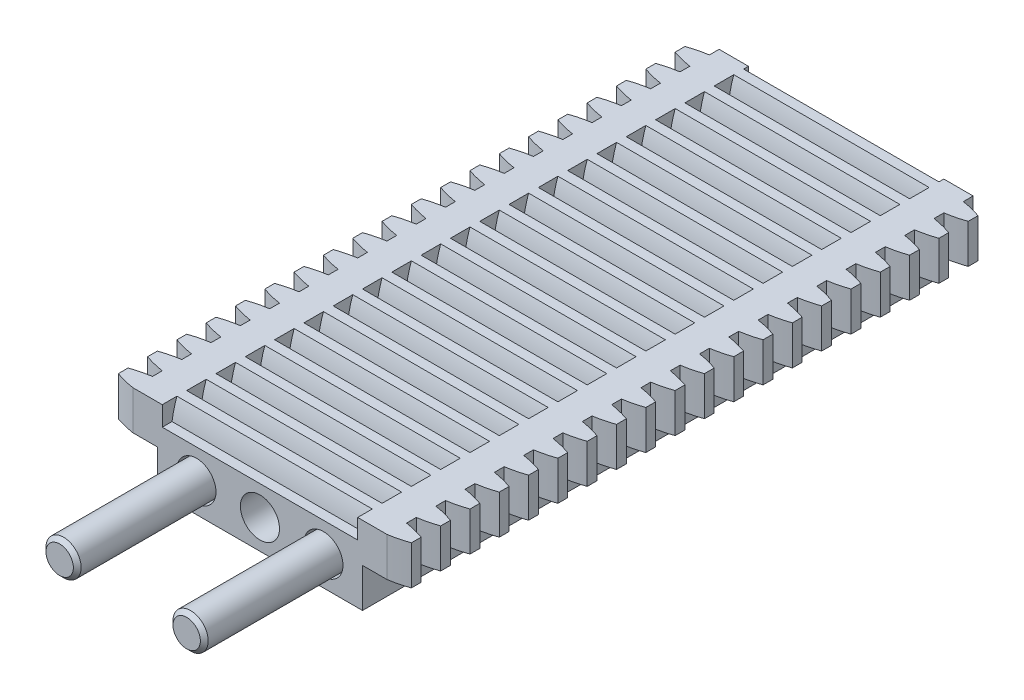
SolidWorks part; units mm, degrees
ref_plane "前视基准面" through (0, 0, 0) normal (0, 0, 1) x (1, 0, 0)
ref_plane "上视基准面" through (0, 0, 0) normal (0, 1, 0) x (1, 0, 0)
ref_plane "右视基准面" through (0, 0, 0) normal (1, 0, 0) x (0, 0, -1)
sketch "草图1" plane through (0, 0, 0) normal (0, 0, 1) x (1, 0, 0)
  line L0 (5.25, 2) -> (6.5, 2)
  line L1 (-5.25, 0) -> (5.25, 0)
  line L2 (-5.25, 0) -> (-5.25, 2)
  line L4 (5.25, 0) -> (5.25, 2)
  line L5 (-6.5, 2) -> (-5.25, 2)
  line L6 (-6.5, 2) -> (-6.5, 4)
  line L7 (-6.5, 4) -> (6.5, 4)
  line L8 (6.5, 2) -> (6.5, 4)
extrude "凸台-拉伸1" add sketch "草图1" against normal blind 60
sketch "草图2" plane through (0, 0, 0) normal (0, 0, 1) x (1, 0, 0)
  line L0 (-1.95, -2.5) -> (-1.1658, -2.5)
  line L1 (-1.95, -2.5) -> (-1.95, -1.5556)
  line L2 (-5.25, 0) -> (5.25, 0) construction
  line L3 (1.95, -2.5) -> (1.95, -1.5556)
  line L4 (0, 0) -> (-1.1658, -2.5)
  line L5 (-1.5, 0) -> (0, 0)
  line L6 (-1.5, 0) -> (-1.5, -0.6771)
  line L7 (0, 0) -> (1.1658, -2.5)
  line L8 (1.5, 0) -> (1.5, -0.6771)
  line L9 (1.1658, -2.5) -> (1.95, -2.5)
  line L10 (0, 0) -> (1.5, 0)
  arc A0 (-1.5, -0.6771) -> (-1.95, -1.5556) centre (0, -2) ccw
  arc A2 (1.95, -1.5556) -> (1.5, -0.6771) centre (0, -2) ccw
  line M2 (-5.25, 0) -> (5.25, 0)
extrude "凸台-拉伸2" add sketch "草图2" against normal blind 54 from offset 3 contours L6 A0 L1 L0 L4 M2 | L3 A2 L8 L7 L9 M2 region at (-1.1423, -1.1553, 0) region at (1.1423, -1.1553, 0) offset against normal yes
sketch "草图3" plane through (0, 0, 0) normal (0, 0, 1) x (1, 0, 0)
  circle A0 centre (-3.25, 1.5) radius 1
  circle A1 centre (0, 1.5) radius 1
  circle A2 centre (3.25, 1.5) radius 1
extrude "切除-拉伸1" cut sketch "草图3" against normal through all
sketch "草图4" plane through (0, 0, 0) normal (0, 0, 1) x (1, 0, 0)
  circle A0 centre (-3.25, 1.5) radius 0.9
  circle A1 centre (3.25, 1.5) radius 0.9
extrude "凸台-拉伸3" add sketch "草图4" along normal blind 7 and the other way blind 7 separate body
fillet "圆角1" radius 0.1 8 edges at (-1.1658, -2.5, -30) (-1.5579, -2.5, -57) (-1.95, -2.5, -30) (-1.5579, -2.5, -3) (1.95, -2.5, -30) (1.5579, -2.5, -57) (1.1658, -2.5, -30) (1.5579, -2.5, -3)
chamfer "倒角2" distance 0.2 angle 45 1 edges at (-2.35, 1.5, 7)
chamfer "倒角3" distance 0.2 angle 45 1 edges at (4.15, 1.5, 7)
sketch "草图6" plane through (0, 4, 0) normal (0, 1, 0) x (1, 0, 0)
  line L0 (-6.5, 59.5) -> (-6.5, 58.5)
  line L1 (-6.5, 60) -> (-6.5, 0) construction
  line L2 (-6.5, 58) -> (-6.5, 57)
  line L3 (-7.5, 59.25) -> (-7.5, 58.75)
  line L4 (-7.5, 57.75) -> (-7.5, 57.25)
  line L5 (-7.5, 56.25) -> (-7.5, 55.75)
  line L6 (-6.5, 56.5) -> (-6.5, 55.5)
  line L7 (-7.5, 54.75) -> (-7.5, 54.25)
  line L8 (-6.5, 55) -> (-6.5, 54)
  line L9 (-7.5, 53.25) -> (-7.5, 52.75)
  line L10 (-6.5, 53.5) -> (-6.5, 52.5)
  line L11 (-7.5, 51.75) -> (-7.5, 51.25)
  line L12 (-6.5, 52) -> (-6.5, 51)
  line L13 (-7.5, 50.25) -> (-7.5, 49.75)
  line L14 (-6.5, 50.5) -> (-6.5, 49.5)
  line L15 (-7.5, 48.75) -> (-7.5, 48.25)
  line L16 (-6.5, 49) -> (-6.5, 48)
  line L17 (-7.5, 47.25) -> (-7.5, 46.75)
  line L18 (-6.5, 47.5) -> (-6.5, 46.5)
  line L19 (-7.5, 45.75) -> (-7.5, 45.25)
  line L20 (-6.5, 46) -> (-6.5, 45)
  line L21 (-7.5, 44.25) -> (-7.5, 43.75)
  line L22 (-6.5, 44.5) -> (-6.5, 43.5)
  line L23 (-7.5, 42.75) -> (-7.5, 42.25)
  line L24 (-6.5, 43) -> (-6.5, 42)
  line L25 (-7.5, 41.25) -> (-7.5, 40.75)
  line L26 (-6.5, 41.5) -> (-6.5, 40.5)
  line L27 (-7.5, 39.75) -> (-7.5, 39.25)
  line L28 (-6.5, 40) -> (-6.5, 39)
  line L29 (-7.5, 38.25) -> (-7.5, 37.75)
  line L30 (-6.5, 38.5) -> (-6.5, 37.5)
  line L31 (-7.5, 36.75) -> (-7.5, 36.25)
  line L32 (-6.5, 37) -> (-6.5, 36)
  line L33 (-7.5, 35.25) -> (-7.5, 34.75)
  line L34 (-6.5, 35.5) -> (-6.5, 34.5)
  line L35 (-7.5, 33.75) -> (-7.5, 33.25)
  line L36 (-6.5, 34) -> (-6.5, 33)
  line L37 (-7.5, 32.25) -> (-7.5, 31.75)
  line L38 (-6.5, 32.5) -> (-6.5, 31.5)
  line L39 (-7.5, 30.75) -> (-7.5, 30.25)
  line L40 (-6.5, 31) -> (-6.5, 30)
  line L41 (-7.5, 29.25) -> (-7.5, 28.75)
  line L42 (-6.5, 29.5) -> (-6.5, 28.5)
  line L43 (-7.5, 27.75) -> (-7.5, 27.25)
  line L44 (-6.5, 28) -> (-6.5, 27)
  line L45 (-7.5, 26.25) -> (-7.5, 25.75)
  line L46 (-6.5, 26.5) -> (-6.5, 25.5)
  line L47 (-7.5, 24.75) -> (-7.5, 24.25)
  line L48 (-6.5, 25) -> (-6.5, 24)
  line L49 (-7.5, 23.25) -> (-7.5, 22.75)
  line L50 (-6.5, 23.5) -> (-6.5, 22.5)
  line L51 (-7.5, 21.75) -> (-7.5, 21.25)
  line L52 (-6.5, 22) -> (-6.5, 21)
  line L53 (-7.5, 20.25) -> (-7.5, 19.75)
  line L54 (-6.5, 20.5) -> (-6.5, 19.5)
  line L55 (-7.5, 18.75) -> (-7.5, 18.25)
  line L56 (-6.5, 19) -> (-6.5, 18)
  line L57 (-7.5, 17.25) -> (-7.5, 16.75)
  line L58 (-6.5, 17.5) -> (-6.5, 16.5)
  line L59 (-7.5, 15.75) -> (-7.5, 15.25)
  line L60 (-6.5, 16) -> (-6.5, 15)
  line L61 (-7.5, 14.25) -> (-7.5, 13.75)
  line L62 (-6.5, 14.5) -> (-6.5, 13.5)
  line L63 (-7.5, 12.75) -> (-7.5, 12.25)
  line L64 (-6.5, 13) -> (-6.5, 12)
  line L65 (-7.5, 11.25) -> (-7.5, 10.75)
  line L66 (-6.5, 11.5) -> (-6.5, 10.5)
  line L67 (-7.5, 9.75) -> (-7.5, 9.25)
  line L68 (-6.5, 10) -> (-6.5, 9)
  line L69 (-7.5, 8.25) -> (-7.5, 7.75)
  line L70 (-6.5, 8.5) -> (-6.5, 7.5)
  line L71 (-7.5, 6.75) -> (-7.5, 6.25)
  line L72 (-6.5, 7) -> (-6.5, 6)
  line L73 (-7.5, 5.25) -> (-7.5, 4.75)
  line L74 (-6.5, 5.5) -> (-6.5, 4.5)
  line L75 (-7.5, 3.75) -> (-7.5, 3.25)
  line L76 (-6.5, 4) -> (-6.5, 3)
  line L77 (-7.5, 2.25) -> (-7.5, 1.75)
  line L78 (-6.5, 2.5) -> (-6.5, 1.5)
  line L79 (-6.5, 1) -> (-6.5, 0)
  line L80 (-7.5, 0.75) -> (-7.5, 0.25)
  line L81 (0, 62.425) -> (0, -2.925) construction
  line L82 (7.5, 0.75) -> (7.5, 0.25)
  line L83 (6.5, 1) -> (6.5, 0)
  line L84 (6.5, 2.5) -> (6.5, 1.5)
  line L85 (7.5, 2.25) -> (7.5, 1.75)
  line L86 (6.5, 4) -> (6.5, 3)
  line L87 (7.5, 3.75) -> (7.5, 3.25)
  line L88 (6.5, 5.5) -> (6.5, 4.5)
  line L89 (7.5, 5.25) -> (7.5, 4.75)
  line L90 (6.5, 7) -> (6.5, 6)
  line L91 (7.5, 6.75) -> (7.5, 6.25)
  line L92 (6.5, 8.5) -> (6.5, 7.5)
  line L93 (7.5, 8.25) -> (7.5, 7.75)
  line L94 (6.5, 10) -> (6.5, 9)
  line L95 (7.5, 9.75) -> (7.5, 9.25)
  line L96 (6.5, 11.5) -> (6.5, 10.5)
  line L97 (7.5, 11.25) -> (7.5, 10.75)
  line L98 (6.5, 13) -> (6.5, 12)
  line L99 (7.5, 12.75) -> (7.5, 12.25)
  line L100 (6.5, 14.5) -> (6.5, 13.5)
  line L101 (7.5, 14.25) -> (7.5, 13.75)
  line L102 (6.5, 16) -> (6.5, 15)
  line L103 (7.5, 15.75) -> (7.5, 15.25)
  line L104 (6.5, 17.5) -> (6.5, 16.5)
  line L105 (7.5, 17.25) -> (7.5, 16.75)
  line L106 (6.5, 19) -> (6.5, 18)
  line L107 (7.5, 18.75) -> (7.5, 18.25)
  line L108 (6.5, 20.5) -> (6.5, 19.5)
  line L109 (7.5, 20.25) -> (7.5, 19.75)
  line L110 (6.5, 22) -> (6.5, 21)
  line L111 (7.5, 21.75) -> (7.5, 21.25)
  line L112 (6.5, 23.5) -> (6.5, 22.5)
  line L113 (7.5, 23.25) -> (7.5, 22.75)
  line L114 (6.5, 25) -> (6.5, 24)
  line L115 (7.5, 24.75) -> (7.5, 24.25)
  line L116 (6.5, 26.5) -> (6.5, 25.5)
  line L117 (7.5, 26.25) -> (7.5, 25.75)
  line L118 (6.5, 28) -> (6.5, 27)
  line L119 (7.5, 27.75) -> (7.5, 27.25)
  line L120 (6.5, 29.5) -> (6.5, 28.5)
  line L121 (7.5, 29.25) -> (7.5, 28.75)
  line L122 (6.5, 31) -> (6.5, 30)
  line L123 (7.5, 30.75) -> (7.5, 30.25)
  line L124 (6.5, 32.5) -> (6.5, 31.5)
  line L125 (7.5, 32.25) -> (7.5, 31.75)
  line L126 (6.5, 34) -> (6.5, 33)
  line L127 (7.5, 33.75) -> (7.5, 33.25)
  line L128 (6.5, 35.5) -> (6.5, 34.5)
  line L129 (7.5, 35.25) -> (7.5, 34.75)
  line L130 (6.5, 37) -> (6.5, 36)
  line L131 (7.5, 36.75) -> (7.5, 36.25)
  line L132 (6.5, 38.5) -> (6.5, 37.5)
  line L133 (7.5, 38.25) -> (7.5, 37.75)
  line L134 (6.5, 40) -> (6.5, 39)
  line L135 (7.5, 39.75) -> (7.5, 39.25)
  line L136 (6.5, 41.5) -> (6.5, 40.5)
  line L137 (7.5, 41.25) -> (7.5, 40.75)
  line L138 (6.5, 43) -> (6.5, 42)
  line L139 (7.5, 42.75) -> (7.5, 42.25)
  line L140 (6.5, 44.5) -> (6.5, 43.5)
  line L141 (7.5, 44.25) -> (7.5, 43.75)
  line L142 (6.5, 46) -> (6.5, 45)
  line L143 (7.5, 45.75) -> (7.5, 45.25)
  line L144 (6.5, 47.5) -> (6.5, 46.5)
  line L145 (7.5, 47.25) -> (7.5, 46.75)
  line L146 (6.5, 49) -> (6.5, 48)
  line L147 (7.5, 48.75) -> (7.5, 48.25)
  line L148 (6.5, 50.5) -> (6.5, 49.5)
  line L149 (7.5, 50.25) -> (7.5, 49.75)
  line L150 (6.5, 52) -> (6.5, 51)
  line L151 (7.5, 51.75) -> (7.5, 51.25)
  line L152 (6.5, 53.5) -> (6.5, 52.5)
  line L153 (7.5, 53.25) -> (7.5, 52.75)
  line L154 (6.5, 55) -> (6.5, 54)
  line L155 (7.5, 54.75) -> (7.5, 54.25)
  line L156 (6.5, 56.5) -> (6.5, 55.5)
  line L157 (7.5, 56.25) -> (7.5, 55.75)
  line L158 (7.5, 57.75) -> (7.5, 57.25)
  line L159 (7.5, 59.25) -> (7.5, 58.75)
  line L160 (6.5, 58) -> (6.5, 57)
  line L161 (6.5, 59.5) -> (6.5, 58.5)
  arc A0 (-7.5, 58.75) -> (-6.5, 58.5) centre (-5.675, 63.925) ccw
  arc A1 (-7.5, 59.25) -> (-6.5, 59.5) centre (-5.675, 54.075) cw
  arc A2 (-7.5, 57.25) -> (-6.5, 57) centre (-5.675, 62.425) ccw
  arc A3 (-7.5, 57.75) -> (-6.5, 58) centre (-5.675, 52.575) cw
  arc A4 (-7.5, 54.25) -> (-6.5, 54) centre (-5.675, 59.425) ccw
  arc A5 (-7.5, 56.25) -> (-6.5, 56.5) centre (-5.675, 51.075) cw
  arc A6 (-7.5, 54.75) -> (-6.5, 55) centre (-5.675, 49.575) cw
  arc A7 (-7.5, 55.75) -> (-6.5, 55.5) centre (-5.675, 60.925) ccw
  arc A8 (-7.5, 51.25) -> (-6.5, 51) centre (-5.675, 56.425) ccw
  arc A9 (-7.5, 53.25) -> (-6.5, 53.5) centre (-5.675, 48.075) cw
  arc A10 (-7.5, 51.75) -> (-6.5, 52) centre (-5.675, 46.575) cw
  arc A11 (-7.5, 52.75) -> (-6.5, 52.5) centre (-5.675, 57.925) ccw
  arc A12 (-7.5, 48.25) -> (-6.5, 48) centre (-5.675, 53.425) ccw
  arc A13 (-7.5, 50.25) -> (-6.5, 50.5) centre (-5.675, 45.075) cw
  arc A14 (-7.5, 48.75) -> (-6.5, 49) centre (-5.675, 43.575) cw
  arc A15 (-7.5, 49.75) -> (-6.5, 49.5) centre (-5.675, 54.925) ccw
  arc A16 (-7.5, 45.25) -> (-6.5, 45) centre (-5.675, 50.425) ccw
  arc A17 (-7.5, 47.25) -> (-6.5, 47.5) centre (-5.675, 42.075) cw
  arc A18 (-7.5, 45.75) -> (-6.5, 46) centre (-5.675, 40.575) cw
  arc A19 (-7.5, 46.75) -> (-6.5, 46.5) centre (-5.675, 51.925) ccw
  arc A20 (-7.5, 42.25) -> (-6.5, 42) centre (-5.675, 47.425) ccw
  arc A21 (-7.5, 44.25) -> (-6.5, 44.5) centre (-5.675, 39.075) cw
  arc A22 (-7.5, 42.75) -> (-6.5, 43) centre (-5.675, 37.575) cw
  arc A23 (-7.5, 43.75) -> (-6.5, 43.5) centre (-5.675, 48.925) ccw
  arc A24 (-7.5, 39.25) -> (-6.5, 39) centre (-5.675, 44.425) ccw
  arc A25 (-7.5, 41.25) -> (-6.5, 41.5) centre (-5.675, 36.075) cw
  arc A26 (-7.5, 39.75) -> (-6.5, 40) centre (-5.675, 34.575) cw
  arc A27 (-7.5, 40.75) -> (-6.5, 40.5) centre (-5.675, 45.925) ccw
  arc A28 (-7.5, 36.25) -> (-6.5, 36) centre (-5.675, 41.425) ccw
  arc A29 (-7.5, 38.25) -> (-6.5, 38.5) centre (-5.675, 33.075) cw
  arc A30 (-7.5, 36.75) -> (-6.5, 37) centre (-5.675, 31.575) cw
  arc A31 (-7.5, 37.75) -> (-6.5, 37.5) centre (-5.675, 42.925) ccw
  arc A32 (-7.5, 33.25) -> (-6.5, 33) centre (-5.675, 38.425) ccw
  arc A33 (-7.5, 35.25) -> (-6.5, 35.5) centre (-5.675, 30.075) cw
  arc A34 (-7.5, 33.75) -> (-6.5, 34) centre (-5.675, 28.575) cw
  arc A35 (-7.5, 34.75) -> (-6.5, 34.5) centre (-5.675, 39.925) ccw
  arc A36 (-7.5, 30.25) -> (-6.5, 30) centre (-5.675, 35.425) ccw
  arc A37 (-7.5, 32.25) -> (-6.5, 32.5) centre (-5.675, 27.075) cw
  arc A38 (-7.5, 30.75) -> (-6.5, 31) centre (-5.675, 25.575) cw
  arc A39 (-7.5, 31.75) -> (-6.5, 31.5) centre (-5.675, 36.925) ccw
  arc A40 (-7.5, 27.25) -> (-6.5, 27) centre (-5.675, 32.425) ccw
  arc A41 (-7.5, 29.25) -> (-6.5, 29.5) centre (-5.675, 24.075) cw
  arc A42 (-7.5, 27.75) -> (-6.5, 28) centre (-5.675, 22.575) cw
  arc A43 (-7.5, 28.75) -> (-6.5, 28.5) centre (-5.675, 33.925) ccw
  arc A44 (-7.5, 24.25) -> (-6.5, 24) centre (-5.675, 29.425) ccw
  arc A45 (-7.5, 26.25) -> (-6.5, 26.5) centre (-5.675, 21.075) cw
  arc A46 (-7.5, 24.75) -> (-6.5, 25) centre (-5.675, 19.575) cw
  arc A47 (-7.5, 25.75) -> (-6.5, 25.5) centre (-5.675, 30.925) ccw
  arc A48 (-7.5, 21.25) -> (-6.5, 21) centre (-5.675, 26.425) ccw
  arc A49 (-7.5, 23.25) -> (-6.5, 23.5) centre (-5.675, 18.075) cw
  arc A50 (-7.5, 21.75) -> (-6.5, 22) centre (-5.675, 16.575) cw
  arc A51 (-7.5, 22.75) -> (-6.5, 22.5) centre (-5.675, 27.925) ccw
  arc A52 (-7.5, 18.25) -> (-6.5, 18) centre (-5.675, 23.425) ccw
  arc A53 (-7.5, 20.25) -> (-6.5, 20.5) centre (-5.675, 15.075) cw
  arc A54 (-7.5, 18.75) -> (-6.5, 19) centre (-5.675, 13.575) cw
  arc A55 (-7.5, 19.75) -> (-6.5, 19.5) centre (-5.675, 24.925) ccw
  arc A56 (-7.5, 15.25) -> (-6.5, 15) centre (-5.675, 20.425) ccw
  arc A57 (-7.5, 17.25) -> (-6.5, 17.5) centre (-5.675, 12.075) cw
  arc A58 (-7.5, 15.75) -> (-6.5, 16) centre (-5.675, 10.575) cw
  arc A59 (-7.5, 16.75) -> (-6.5, 16.5) centre (-5.675, 21.925) ccw
  arc A60 (-7.5, 12.25) -> (-6.5, 12) centre (-5.675, 17.425) ccw
  arc A61 (-7.5, 14.25) -> (-6.5, 14.5) centre (-5.675, 9.075) cw
  arc A62 (-7.5, 12.75) -> (-6.5, 13) centre (-5.675, 7.575) cw
  arc A63 (-7.5, 13.75) -> (-6.5, 13.5) centre (-5.675, 18.925) ccw
  arc A64 (-7.5, 9.25) -> (-6.5, 9) centre (-5.675, 14.425) ccw
  arc A65 (-7.5, 11.25) -> (-6.5, 11.5) centre (-5.675, 6.075) cw
  arc A66 (-7.5, 9.75) -> (-6.5, 10) centre (-5.675, 4.575) cw
  arc A67 (-7.5, 10.75) -> (-6.5, 10.5) centre (-5.675, 15.925) ccw
  arc A68 (-7.5, 6.25) -> (-6.5, 6) centre (-5.675, 11.425) ccw
  arc A69 (-7.5, 8.25) -> (-6.5, 8.5) centre (-5.675, 3.075) cw
  arc A70 (-7.5, 6.75) -> (-6.5, 7) centre (-5.675, 1.575) cw
  arc A71 (-7.5, 7.75) -> (-6.5, 7.5) centre (-5.675, 12.925) ccw
  arc A72 (-7.5, 3.25) -> (-6.5, 3) centre (-5.675, 8.425) ccw
  arc A73 (-7.5, 5.25) -> (-6.5, 5.5) centre (-5.675, 0.075) cw
  arc A74 (-7.5, 3.75) -> (-6.5, 4) centre (-5.675, -1.425) cw
  arc A75 (-7.5, 4.75) -> (-6.5, 4.5) centre (-5.675, 9.925) ccw
  arc A76 (-7.5, 1.75) -> (-6.5, 1.5) centre (-5.675, 6.925) ccw
  arc A77 (-7.5, 2.25) -> (-6.5, 2.5) centre (-5.675, -2.925) cw
  arc A78 (-7.5, 0.25) -> (-6.5, 0) centre (-5.675, 5.425) ccw
  arc A79 (-7.5, 0.75) -> (-6.5, 1) centre (-5.675, -4.425) cw
  arc A80 (7.5, 0.75) -> (6.5, 1) centre (5.675, -4.425) ccw
  arc A81 (7.5, 0.25) -> (6.5, 0) centre (5.675, 5.425) cw
  arc A82 (7.5, 2.25) -> (6.5, 2.5) centre (5.675, -2.925) ccw
  arc A83 (7.5, 1.75) -> (6.5, 1.5) centre (5.675, 6.925) cw
  arc A84 (7.5, 4.75) -> (6.5, 4.5) centre (5.675, 9.925) cw
  arc A85 (7.5, 3.75) -> (6.5, 4) centre (5.675, -1.425) ccw
  arc A86 (7.5, 5.25) -> (6.5, 5.5) centre (5.675, 0.075) ccw
  arc A87 (7.5, 3.25) -> (6.5, 3) centre (5.675, 8.425) cw
  arc A88 (7.5, 7.75) -> (6.5, 7.5) centre (5.675, 12.925) cw
  arc A89 (7.5, 6.75) -> (6.5, 7) centre (5.675, 1.575) ccw
  arc A90 (7.5, 8.25) -> (6.5, 8.5) centre (5.675, 3.075) ccw
  arc A91 (7.5, 6.25) -> (6.5, 6) centre (5.675, 11.425) cw
  arc A92 (7.5, 10.75) -> (6.5, 10.5) centre (5.675, 15.925) cw
  arc A93 (7.5, 9.75) -> (6.5, 10) centre (5.675, 4.575) ccw
  arc A94 (7.5, 11.25) -> (6.5, 11.5) centre (5.675, 6.075) ccw
  arc A95 (7.5, 9.25) -> (6.5, 9) centre (5.675, 14.425) cw
  arc A96 (7.5, 13.75) -> (6.5, 13.5) centre (5.675, 18.925) cw
  arc A97 (7.5, 12.75) -> (6.5, 13) centre (5.675, 7.575) ccw
  arc A98 (7.5, 14.25) -> (6.5, 14.5) centre (5.675, 9.075) ccw
  arc A99 (7.5, 12.25) -> (6.5, 12) centre (5.675, 17.425) cw
  arc A100 (7.5, 16.75) -> (6.5, 16.5) centre (5.675, 21.925) cw
  arc A101 (7.5, 15.75) -> (6.5, 16) centre (5.675, 10.575) ccw
  arc A102 (7.5, 17.25) -> (6.5, 17.5) centre (5.675, 12.075) ccw
  arc A103 (7.5, 15.25) -> (6.5, 15) centre (5.675, 20.425) cw
  arc A104 (7.5, 19.75) -> (6.5, 19.5) centre (5.675, 24.925) cw
  arc A105 (7.5, 18.75) -> (6.5, 19) centre (5.675, 13.575) ccw
  arc A106 (7.5, 20.25) -> (6.5, 20.5) centre (5.675, 15.075) ccw
  arc A107 (7.5, 18.25) -> (6.5, 18) centre (5.675, 23.425) cw
  arc A108 (7.5, 22.75) -> (6.5, 22.5) centre (5.675, 27.925) cw
  arc A109 (7.5, 21.75) -> (6.5, 22) centre (5.675, 16.575) ccw
  arc A110 (7.5, 23.25) -> (6.5, 23.5) centre (5.675, 18.075) ccw
  arc A111 (7.5, 21.25) -> (6.5, 21) centre (5.675, 26.425) cw
  arc A112 (7.5, 25.75) -> (6.5, 25.5) centre (5.675, 30.925) cw
  arc A113 (7.5, 24.75) -> (6.5, 25) centre (5.675, 19.575) ccw
  arc A114 (7.5, 26.25) -> (6.5, 26.5) centre (5.675, 21.075) ccw
  arc A115 (7.5, 24.25) -> (6.5, 24) centre (5.675, 29.425) cw
  arc A116 (7.5, 28.75) -> (6.5, 28.5) centre (5.675, 33.925) cw
  arc A117 (7.5, 27.75) -> (6.5, 28) centre (5.675, 22.575) ccw
  arc A118 (7.5, 29.25) -> (6.5, 29.5) centre (5.675, 24.075) ccw
  arc A119 (7.5, 27.25) -> (6.5, 27) centre (5.675, 32.425) cw
  arc A120 (7.5, 31.75) -> (6.5, 31.5) centre (5.675, 36.925) cw
  arc A121 (7.5, 30.75) -> (6.5, 31) centre (5.675, 25.575) ccw
  arc A122 (7.5, 32.25) -> (6.5, 32.5) centre (5.675, 27.075) ccw
  arc A123 (7.5, 30.25) -> (6.5, 30) centre (5.675, 35.425) cw
  arc A124 (7.5, 34.75) -> (6.5, 34.5) centre (5.675, 39.925) cw
  arc A125 (7.5, 33.75) -> (6.5, 34) centre (5.675, 28.575) ccw
  arc A126 (7.5, 35.25) -> (6.5, 35.5) centre (5.675, 30.075) ccw
  arc A127 (7.5, 33.25) -> (6.5, 33) centre (5.675, 38.425) cw
  arc A128 (7.5, 37.75) -> (6.5, 37.5) centre (5.675, 42.925) cw
  arc A129 (7.5, 36.75) -> (6.5, 37) centre (5.675, 31.575) ccw
  arc A130 (7.5, 38.25) -> (6.5, 38.5) centre (5.675, 33.075) ccw
  arc A131 (7.5, 36.25) -> (6.5, 36) centre (5.675, 41.425) cw
  arc A132 (7.5, 40.75) -> (6.5, 40.5) centre (5.675, 45.925) cw
  arc A133 (7.5, 39.75) -> (6.5, 40) centre (5.675, 34.575) ccw
  arc A134 (7.5, 41.25) -> (6.5, 41.5) centre (5.675, 36.075) ccw
  arc A135 (7.5, 39.25) -> (6.5, 39) centre (5.675, 44.425) cw
  arc A136 (7.5, 43.75) -> (6.5, 43.5) centre (5.675, 48.925) cw
  arc A137 (7.5, 42.75) -> (6.5, 43) centre (5.675, 37.575) ccw
  arc A138 (7.5, 44.25) -> (6.5, 44.5) centre (5.675, 39.075) ccw
  arc A139 (7.5, 42.25) -> (6.5, 42) centre (5.675, 47.425) cw
  arc A140 (7.5, 46.75) -> (6.5, 46.5) centre (5.675, 51.925) cw
  arc A141 (7.5, 45.75) -> (6.5, 46) centre (5.675, 40.575) ccw
  arc A142 (7.5, 47.25) -> (6.5, 47.5) centre (5.675, 42.075) ccw
  arc A143 (7.5, 45.25) -> (6.5, 45) centre (5.675, 50.425) cw
  arc A144 (7.5, 49.75) -> (6.5, 49.5) centre (5.675, 54.925) cw
  arc A145 (7.5, 48.75) -> (6.5, 49) centre (5.675, 43.575) ccw
  arc A146 (7.5, 50.25) -> (6.5, 50.5) centre (5.675, 45.075) ccw
  arc A147 (7.5, 48.25) -> (6.5, 48) centre (5.675, 53.425) cw
  arc A148 (7.5, 52.75) -> (6.5, 52.5) centre (5.675, 57.925) cw
  arc A149 (7.5, 51.75) -> (6.5, 52) centre (5.675, 46.575) ccw
  arc A150 (7.5, 53.25) -> (6.5, 53.5) centre (5.675, 48.075) ccw
  arc A151 (7.5, 51.25) -> (6.5, 51) centre (5.675, 56.425) cw
  arc A152 (7.5, 55.75) -> (6.5, 55.5) centre (5.675, 60.925) cw
  arc A153 (7.5, 54.75) -> (6.5, 55) centre (5.675, 49.575) ccw
  arc A154 (7.5, 56.25) -> (6.5, 56.5) centre (5.675, 51.075) ccw
  arc A155 (7.5, 54.25) -> (6.5, 54) centre (5.675, 59.425) cw
  arc A156 (7.5, 57.75) -> (6.5, 58) centre (5.675, 52.575) ccw
  arc A157 (7.5, 57.25) -> (6.5, 57) centre (5.675, 62.425) cw
  arc A158 (7.5, 59.25) -> (6.5, 59.5) centre (5.675, 54.075) ccw
  arc A159 (7.5, 58.75) -> (6.5, 58.5) centre (5.675, 63.925) cw
extrude "凸台-拉伸4" add sketch "草图6" against normal up to surface (2 mm away) up to face at (-5.875, 2, -30)
sketch "草图7" plane through (0, 0, 0) normal (1, 0, 0) x (0, 0, -1)
  line L0 (2.75, 4) -> (3.75, 4)
  line L1 (1.25, 4) -> (1, 4) construction
  line L2 (3, 3) -> (3.5, 3)
  line L3 (1.5, 4) -> (1, 4) construction
  line L4 (4.25, 4) -> (5.25, 4)
  line L5 (1.5, 3) -> (2, 3)
  line L6 (1, 4) -> (1, 3.5939) construction
  line L7 (4.5, 3) -> (5, 3)
  line L8 (0.5, 3) -> (0, 3)
  line L9 (1.25, 4) -> (2.25, 4)
  line L10 (5.75, 4) -> (6.75, 4)
  line L11 (6, 3) -> (6.5, 3)
  line L12 (9, 3) -> (9.5, 3)
  line L13 (11.75, 4) -> (12.75, 4)
  line L14 (8.75, 4) -> (9.75, 4)
  line L15 (10.25, 4) -> (11.25, 4)
  line L16 (7.25, 4) -> (8.25, 4)
  line L17 (12, 3) -> (12.5, 3)
  line L18 (10.5, 3) -> (11, 3)
  line L19 (7.5, 3) -> (8, 3)
  line L20 (15, 3) -> (15.5, 3)
  line L21 (17.75, 4) -> (18.75, 4)
  line L22 (14.75, 4) -> (15.75, 4)
  line L23 (16.25, 4) -> (17.25, 4)
  line L24 (13.25, 4) -> (14.25, 4)
  line L25 (18, 3) -> (18.5, 3)
  line L26 (16.5, 3) -> (17, 3)
  line L27 (13.5, 3) -> (14, 3)
  line L28 (24, 3) -> (24.5, 3)
  line L29 (20.75, 4) -> (21.75, 4)
  line L30 (19.5, 3) -> (20, 3)
  line L31 (21, 3) -> (21.5, 3)
  line L32 (19.25, 4) -> (20.25, 4)
  line L33 (22.25, 4) -> (23.25, 4)
  line L34 (22.5, 3) -> (23, 3)
  line L35 (23.75, 4) -> (24.75, 4)
  line L36 (30, 3) -> (30.5, 3)
  line L37 (26.75, 4) -> (27.75, 4)
  line L38 (25.5, 3) -> (26, 3)
  line L39 (27, 3) -> (27.5, 3)
  line L40 (25.25, 4) -> (26.25, 4)
  line L41 (28.25, 4) -> (29.25, 4)
  line L42 (28.5, 3) -> (29, 3)
  line L43 (29.75, 4) -> (30.75, 4)
  line L44 (36, 3) -> (36.5, 3)
  line L45 (32.75, 4) -> (33.75, 4)
  line L46 (31.5, 3) -> (32, 3)
  line L47 (33, 3) -> (33.5, 3)
  line L48 (31.25, 4) -> (32.25, 4)
  line L49 (34.25, 4) -> (35.25, 4)
  line L50 (34.5, 3) -> (35, 3)
  line L51 (35.75, 4) -> (36.75, 4)
  line L52 (42, 3) -> (42.5, 3)
  line L53 (38.75, 4) -> (39.75, 4)
  line L54 (37.5, 3) -> (38, 3)
  line L55 (39, 3) -> (39.5, 3)
  line L56 (37.25, 4) -> (38.25, 4)
  line L57 (40.25, 4) -> (41.25, 4)
  line L58 (40.5, 3) -> (41, 3)
  line L59 (41.75, 4) -> (42.75, 4)
  line L60 (48, 3) -> (48.5, 3)
  line L61 (44.75, 4) -> (45.75, 4)
  line L62 (43.5, 3) -> (44, 3)
  line L63 (45, 3) -> (45.5, 3)
  line L64 (43.25, 4) -> (44.25, 4)
  line L65 (46.25, 4) -> (47.25, 4)
  line L66 (46.5, 3) -> (47, 3)
  line L67 (47.75, 4) -> (48.75, 4)
  line L68 (54, 3) -> (54.5, 3)
  line L69 (50.75, 4) -> (51.75, 4)
  line L70 (49.5, 3) -> (50, 3)
  line L71 (51, 3) -> (51.5, 3)
  line L72 (49.25, 4) -> (50.25, 4)
  line L73 (52.25, 4) -> (53.25, 4)
  line L74 (52.5, 3) -> (53, 3)
  line L75 (53.75, 4) -> (54.75, 4)
  line L76 (0.75, 4) -> (-0.25, 4)
  line L77 (56.75, 4) -> (57.75, 4)
  line L78 (55.5, 3) -> (56, 3)
  line L79 (57, 3) -> (57.5, 3)
  line L80 (55.25, 4) -> (56.25, 4)
  line L81 (58.25, 4) -> (59.25, 4)
  line L82 (58.5, 3) -> (59, 3)
  line L83 (59.25, 4) -> (59.5, 4) construction
  line L84 (60, 4) -> (59.5, 4) construction
  line L85 (59.5, 4) -> (59.5, 3.5184) construction
  line L86 (60.5, 3) -> (60, 3)
  line L87 (60.75, 4) -> (59.75, 4)
  arc A0 (2.25, 4) -> (2, 3) centre (7.425, 2.175) ccw
  arc A1 (1.25, 4) -> (1.5, 3) centre (-3.925, 2.175) cw
  arc A2 (2.75, 4) -> (3, 3) centre (-2.425, 2.175) cw
  arc A3 (3.75, 4) -> (3.5, 3) centre (8.925, 2.175) ccw
  arc A4 (4.25, 4) -> (4.5, 3) centre (-0.925, 2.175) cw
  arc A5 (5.25, 4) -> (5, 3) centre (10.425, 2.175) ccw
  arc A6 (5.75, 4) -> (6, 3) centre (0.575, 2.175) cw
  arc A7 (6.75, 4) -> (6.5, 3) centre (11.925, 2.175) ccw
  arc A8 (11.25, 4) -> (11, 3) centre (16.425, 2.175) ccw
  arc A9 (8.75, 4) -> (9, 3) centre (3.575, 2.175) cw
  arc A10 (12.75, 4) -> (12.5, 3) centre (17.925, 2.175) ccw
  arc A11 (7.25, 4) -> (7.5, 3) centre (2.075, 2.175) cw
  arc A12 (10.25, 4) -> (10.5, 3) centre (5.075, 2.175) cw
  arc A13 (9.75, 4) -> (9.5, 3) centre (14.925, 2.175) ccw
  arc A14 (11.75, 4) -> (12, 3) centre (6.575, 2.175) cw
  arc A15 (8.25, 4) -> (8, 3) centre (13.425, 2.175) ccw
  arc A16 (17.25, 4) -> (17, 3) centre (22.425, 2.175) ccw
  arc A17 (14.75, 4) -> (15, 3) centre (9.575, 2.175) cw
  arc A18 (18.75, 4) -> (18.5, 3) centre (23.925, 2.175) ccw
  arc A19 (13.25, 4) -> (13.5, 3) centre (8.075, 2.175) cw
  arc A20 (16.25, 4) -> (16.5, 3) centre (11.075, 2.175) cw
  arc A21 (15.75, 4) -> (15.5, 3) centre (20.925, 2.175) ccw
  arc A22 (17.75, 4) -> (18, 3) centre (12.575, 2.175) cw
  arc A23 (14.25, 4) -> (14, 3) centre (19.425, 2.175) ccw
  arc A24 (23.25, 4) -> (23, 3) centre (28.425, 2.175) ccw
  arc A25 (24.75, 4) -> (24.5, 3) centre (29.925, 2.175) ccw
  arc A26 (20.25, 4) -> (20, 3) centre (25.425, 2.175) ccw
  arc A27 (21.75, 4) -> (21.5, 3) centre (26.925, 2.175) ccw
  arc A28 (20.75, 4) -> (21, 3) centre (15.575, 2.175) cw
  arc A29 (22.25, 4) -> (22.5, 3) centre (17.075, 2.175) cw
  arc A30 (19.25, 4) -> (19.5, 3) centre (14.075, 2.175) cw
  arc A31 (23.75, 4) -> (24, 3) centre (18.575, 2.175) cw
  arc A32 (29.25, 4) -> (29, 3) centre (34.425, 2.175) ccw
  arc A33 (30.75, 4) -> (30.5, 3) centre (35.925, 2.175) ccw
  arc A34 (26.25, 4) -> (26, 3) centre (31.425, 2.175) ccw
  arc A35 (27.75, 4) -> (27.5, 3) centre (32.925, 2.175) ccw
  arc A36 (26.75, 4) -> (27, 3) centre (21.575, 2.175) cw
  arc A37 (28.25, 4) -> (28.5, 3) centre (23.075, 2.175) cw
  arc A38 (25.25, 4) -> (25.5, 3) centre (20.075, 2.175) cw
  arc A39 (29.75, 4) -> (30, 3) centre (24.575, 2.175) cw
  arc A40 (35.25, 4) -> (35, 3) centre (40.425, 2.175) ccw
  arc A41 (36.75, 4) -> (36.5, 3) centre (41.925, 2.175) ccw
  arc A42 (32.25, 4) -> (32, 3) centre (37.425, 2.175) ccw
  arc A43 (33.75, 4) -> (33.5, 3) centre (38.925, 2.175) ccw
  arc A44 (32.75, 4) -> (33, 3) centre (27.575, 2.175) cw
  arc A45 (34.25, 4) -> (34.5, 3) centre (29.075, 2.175) cw
  arc A46 (31.25, 4) -> (31.5, 3) centre (26.075, 2.175) cw
  arc A47 (35.75, 4) -> (36, 3) centre (30.575, 2.175) cw
  arc A48 (41.25, 4) -> (41, 3) centre (46.425, 2.175) ccw
  arc A49 (42.75, 4) -> (42.5, 3) centre (47.925, 2.175) ccw
  arc A50 (38.25, 4) -> (38, 3) centre (43.425, 2.175) ccw
  arc A51 (39.75, 4) -> (39.5, 3) centre (44.925, 2.175) ccw
  arc A52 (38.75, 4) -> (39, 3) centre (33.575, 2.175) cw
  arc A53 (40.25, 4) -> (40.5, 3) centre (35.075, 2.175) cw
  arc A54 (37.25, 4) -> (37.5, 3) centre (32.075, 2.175) cw
  arc A55 (41.75, 4) -> (42, 3) centre (36.575, 2.175) cw
  arc A56 (47.25, 4) -> (47, 3) centre (52.425, 2.175) ccw
  arc A57 (48.75, 4) -> (48.5, 3) centre (53.925, 2.175) ccw
  arc A58 (44.25, 4) -> (44, 3) centre (49.425, 2.175) ccw
  arc A59 (45.75, 4) -> (45.5, 3) centre (50.925, 2.175) ccw
  arc A60 (44.75, 4) -> (45, 3) centre (39.575, 2.175) cw
  arc A61 (46.25, 4) -> (46.5, 3) centre (41.075, 2.175) cw
  arc A62 (43.25, 4) -> (43.5, 3) centre (38.075, 2.175) cw
  arc A63 (47.75, 4) -> (48, 3) centre (42.575, 2.175) cw
  arc A64 (53.25, 4) -> (53, 3) centre (58.425, 2.175) ccw
  arc A65 (54.75, 4) -> (54.5, 3) centre (59.925, 2.175) ccw
  arc A66 (50.25, 4) -> (50, 3) centre (55.425, 2.175) ccw
  arc A67 (51.75, 4) -> (51.5, 3) centre (56.925, 2.175) ccw
  arc A68 (50.75, 4) -> (51, 3) centre (45.575, 2.175) cw
  arc A69 (52.25, 4) -> (52.5, 3) centre (47.075, 2.175) cw
  arc A70 (49.25, 4) -> (49.5, 3) centre (44.075, 2.175) cw
  arc A71 (53.75, 4) -> (54, 3) centre (48.575, 2.175) cw
  arc A72 (59.25, 4) -> (59, 3) centre (64.425, 2.175) ccw
  arc A73 (-0.25, 4) -> (0, 3) centre (-5.425, 2.175) cw
  arc A74 (56.25, 4) -> (56, 3) centre (61.425, 2.175) ccw
  arc A75 (57.75, 4) -> (57.5, 3) centre (62.925, 2.175) ccw
  arc A76 (56.75, 4) -> (57, 3) centre (51.575, 2.175) cw
  arc A77 (58.25, 4) -> (58.5, 3) centre (53.075, 2.175) cw
  arc A78 (55.25, 4) -> (55.5, 3) centre (50.075, 2.175) cw
  arc A79 (0.75, 4) -> (0.5, 3) centre (5.925, 2.175) ccw
  arc A80 (59.75, 4) -> (60, 3) centre (54.575, 2.175) cw
  arc A81 (60.75, 4) -> (60.5, 3) centre (65.925, 2.175) ccw
  dimension "D1" = 0.25
  dimension "D2" = 0.25
extrude "切除-拉伸2" cut sketch "草图7" against normal blind 5
extrude "切除-拉伸3" cut sketch "草图7<2>" along normal blind 5
sketch "草图7<2>" plane through (0, 0, 0) normal (1, 0, 0) x (0, 0, -1) same geometry as "草图7"
sketch "草图8" plane through (0, 4, 0) normal (0, 1, 0) x (1, 0, 0)
  line L0 (0, 60) -> (-10, 60)
  line L3 (-5, 60) -> (5, 60) construction
  line L4 (-10, 60) -> (-10, 30)
  line L5 (-10, 30) -> (10, 30)
  line L6 (10, 30) -> (10, 60)
  line L7 (10, 60) -> (0, 60)
  dimension "D1" = 10
  dimension "D2" = 30
  dimension "D3" = 20
extrude "切除-拉伸4" cut sketch "草图8" against normal through all
sketch "草图9" plane through (0, 0, -30) normal (0, 0, -1) x (-1, 0, 0)
  line L0 (0, 0) -> (-2, 0)
  line L1 (-5.25, 0) -> (-1.5, 0) construction
  line L2 (-2, 0) -> (-2, -3)
  line L3 (-2, -3) -> (2, -3)
  line L4 (2, -3) -> (2, 0)
  line L5 (1.5, 0) -> (5.25, 0) construction
  line L6 (2, 0) -> (0, 0)
  dimension "D1" = 2
  dimension "D2" = 3
  dimension "D3" = 4
extrude "切除-拉伸5" cut sketch "草图9" against normal blind 3
